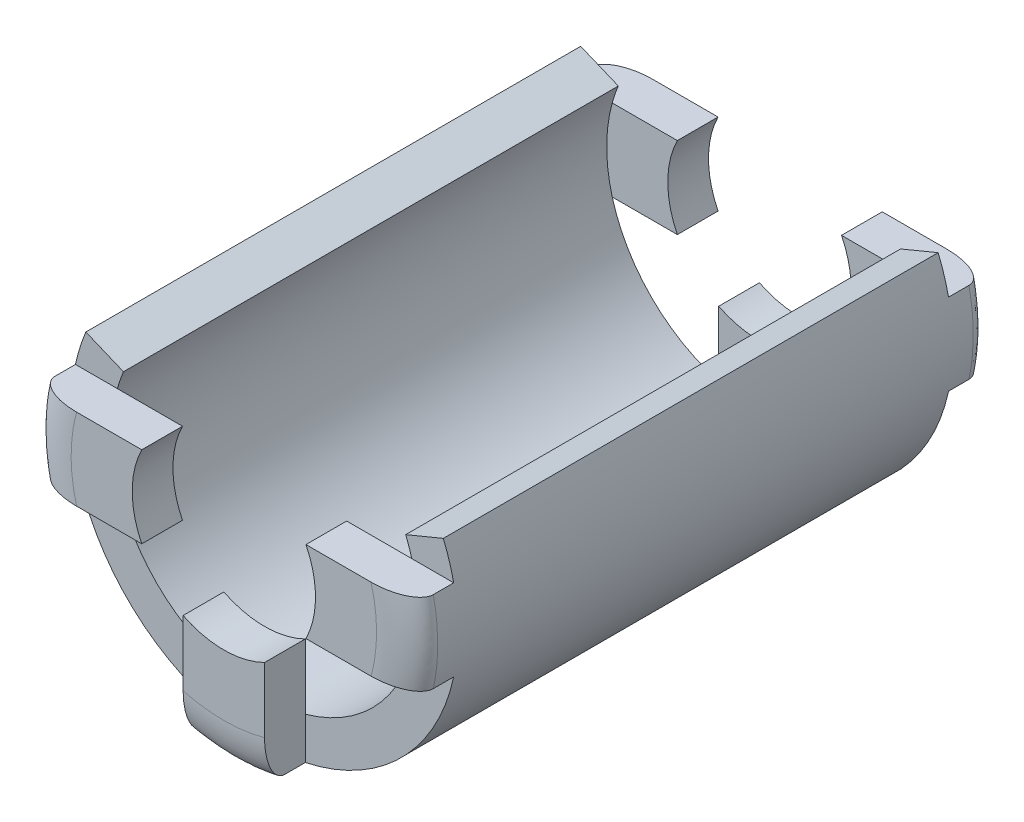
SolidWorks part; units mm, degrees
ref_plane "Front Plane" through (0, 0, 0) normal (0, 0, 1) x (1, 0, 0)
ref_plane "Top Plane" through (0, 0, 0) normal (0, 1, 0) x (1, 0, 0)
ref_plane "Right Plane" through (0, 0, 0) normal (1, 0, 0) x (0, 0, -1)
sketch "Sketch1" plane through (0, 0, 0) normal (0, 0, 1) x (1, 0, 0)
  line L2 (-6.9291, 2.8701) -> (-8.7769, 3.6355)
  line L3 (6.9291, 2.8701) -> (8.7769, 3.6355)
  line L4 (0, 7.5) -> (0, 23.3358) construction
  arc A0 (-6.9291, 2.8701) -> (6.9291, 2.8701) centre (0, 0) ccw
  arc A1 (-8.7769, 3.6355) -> (8.7769, 3.6355) centre (0, 0) ccw
  circle A2 centre (0, 0) radius 9.5 construction
  circle A3 centre (0, 0) radius 7.5 construction
  dimension "D3" = 15
  dimension "D5" = 135
  dimension "D4" = 2
extrude "Boss-Extrude1" add sketch "Sketch1" against normal blind 24.3
sketch "Sketch4" plane through (0, 0, 0) normal (1, 0, 0) x (0, 0, -1)
  line L0 (0, 3.6355) -> (0, -9.5) construction
  circle A0 centre (7.6, -15) radius 7.6
  dimension "D1" = 15.2
  dimension "D2" = 15
extrude "Cut-Extrude3" cut sketch "Sketch4" against normal up to next and the other way up to next
sketch "Sketch6" plane through (0, 0, 0) normal (0, 0, 1) x (1, 0, 0)
  line L0 (0, 0) -> (4.9784, 0) construction
  line L1 (-9.2871, 2) -> (-4.0311, 2)
  line L2 (-9.2871, -2) -> (-4.0311, -2)
  line L3 (0, 0.3063) -> (0, 50000.3063) construction
  line L4 (9.2871, -2) -> (4.0311, -2)
  line L5 (9.2871, 2) -> (4.0311, 2)
  line L6 (0, 0) -> (8.8342, 8.8342) construction
  line L7 (-2, -9.2871) -> (-2, -4.0311)
  line L8 (2, -9.2871) -> (2, -4.0311)
  arc A1 (-9.2871, 2) -> (-9.2871, -2) centre (0, 0) ccw
  arc A3 (-8.7769, 3.6355) -> (8.7769, 3.6355) centre (0, 0) ccw construction
  arc A4 (-4.0311, 2) -> (-4.0311, -2) centre (0, 0) ccw
  arc A5 (-2, -4.0311) -> (2, -4.0311) centre (0, 0) ccw
  arc A6 (4.0311, -2) -> (4.0311, 2) centre (0, 0) ccw
  arc A7 (-2, -9.2871) -> (2, -9.2871) centre (0, 0) ccw
  arc A8 (9.2871, -2) -> (9.2871, 2) centre (0, 0) ccw
  dimension "D2" = 9
  dimension "D1" = 4
extrude "Boss-Extrude2" add sketch "Sketch6" along normal blind 2
ref_plane "Plane1" through (0, 0, -12.15) normal (0, 0, 1) x (1, 0, 0)
mirror "Mirror1" about plane through (0, 0, -12.15) normal (0, 0, 1) of "Boss-Extrude2"
fillet "Fillet1" radius 1 6 edges at (9.5, 0, -26.3) (0, -9.5, -26.3) (-9.5, 0, -26.3) (9.5, 0, 2) (0, -9.5, 2) (-9.5, 0, 2)
sketch "Sketch7" plane through (0, 0, -12.15) normal (0, 0, 1) x (1, 0, 0)
